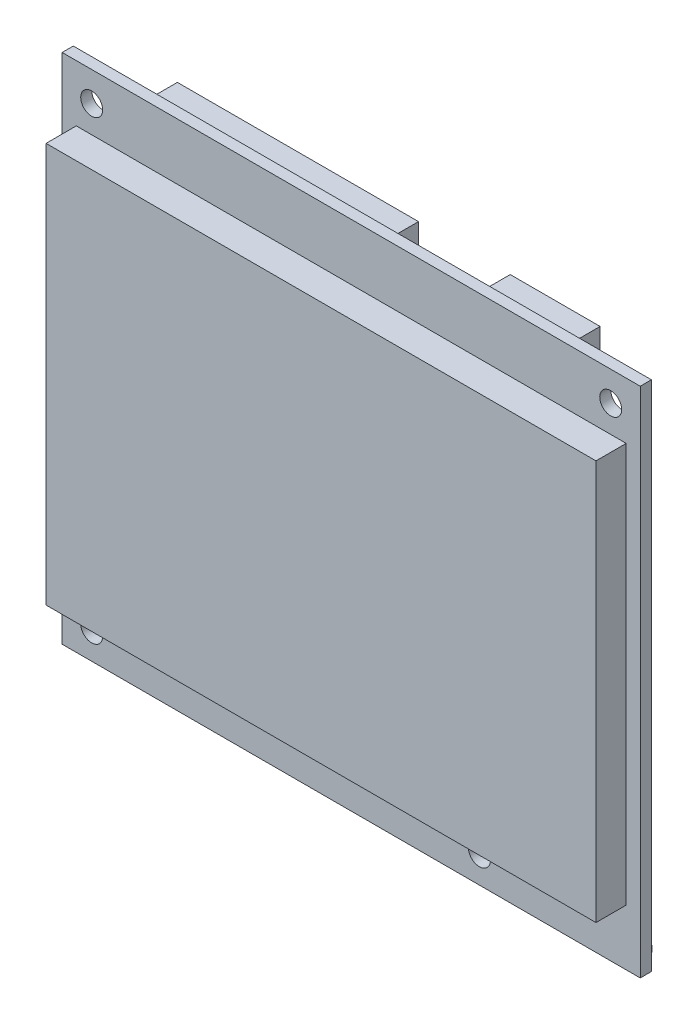
SolidWorks part; units mm, degrees
ref_plane "Front Plane" through (0, 0, 0) normal (0, 0, 1) x (1, 0, 0)
ref_plane "Top Plane" through (0, 0, 0) normal (0, 1, 0) x (1, 0, 0)
ref_plane "Right Plane" through (0, 0, 0) normal (1, 0, 0) x (0, 0, -1)
sketch "Sketch1" plane through (0, 0, 0) normal (0, 0, -1) x (-1, 0, 0)
  line L1 (-32.25, -24.25) -> (32.25, -24.25) construction
  line L2 (-32.25, -24.25) -> (-32.25, 24.25) construction
  line L3 (-32.25, 24.25) -> (32.25, 24.25) construction
  line L4 (32.25, -24.25) -> (32.25, 24.25) construction
  line L5 (-32.25, -24.25) -> (32.25, 24.25) construction
  line L6 (-32.25, 24.25) -> (32.25, -24.25) construction
  line L7 (-36, 28) -> (41.7, 28) construction
  line L8 (-36, 28) -> (-36, -28.5) construction
  line L9 (-36, -28.5) -> (41.7, -28.5) construction
  line L10 (41.7, 28) -> (41.7, -28.5) construction
  line L11 (-37.9864, 35.9904) -> (43.7, 35.9904)
  line L12 (-37.9864, 35.9904) -> (-37.9864, -36.425)
  line L13 (-37.9864, -36.425) -> (43.7, -36.425)
  line L14 (43.7, 35.9904) -> (43.7, -36.425)
  point P0 (0, 0)
  dimension "D1" = 64.5
  dimension "D2" = 48.5
  dimension "D3" = 3.75
  dimension "D4" = 3.75
  dimension "D5" = 56.5
  dimension "D6" = 77.7
  dimension "D7" = 7.925
  dimension "D8" = 72.4154
  dimension "D9" = 81.6864
  dimension "D10" = 2
extrude "Boss-Extrude1" add sketch "Sketch1" along normal blind 1.5748
sketch "Sketch2" plane through (0, 0, 0) normal (0, 0, -1) x (-1, 0, 0)
  line L1 (-36, -28.5) -> (41.7, -28.5)
  line L2 (-36, -28.5) -> (-36, 28)
  line L3 (-36, 28) -> (41.7, 28)
  line L4 (41.7, -28.5) -> (41.7, 28)
  line L5 (41.7, 28) -> (49.6841, 28) construction
  line L6 (-36, 28) -> (-43.9841, 28) construction
  line L10 (-32.25, -24.25) -> (32.25, -24.25) construction
  line L11 (-32.25, -24.25) -> (-32.25, 24.25) construction
  line L12 (-32.25, 24.25) -> (32.25, 24.25) construction
  line L13 (32.25, -24.25) -> (32.25, 24.25) construction
  line L14 (-32.25, -24.25) -> (32.25, 24.25) construction
  line L15 (-32.25, 24.25) -> (32.25, -24.25) construction
  point P0 (0, 0)
  point P14 (0, 0)
  dimension "D1" = 56.5
  dimension "D2" = 77.7
  dimension "D3" = 3.75
  dimension "D4" = 48.5
  dimension "D5" = 64.5
  dimension "D6" = 3.75
extrude "Boss-Extrude2" add sketch "Sketch2" against normal blind 4.27
sketch "Sketch3" plane through (0, 0, -1.5748) normal (0, 0, 1) x (1, 0, 0)
  line L1 (25.66, 33.8141) -> (12.96, 33.8141)
  line L2 (25.66, 33.8141) -> (25.66, 28.7341)
  line L3 (25.66, 28.7341) -> (12.96, 28.7341)
  line L4 (12.96, 33.8141) -> (12.96, 28.7341)
  line L6 (0, 33.8141) -> (-34.0711, 33.8141)
  line L7 (0, 33.8141) -> (0, 28.7341)
  line L8 (0, 28.7341) -> (-34.0711, 28.7341)
  line L9 (-34.0711, 33.8141) -> (-34.0711, 28.7341)
  line L10 (-34.0711, -29.1593) -> (0, -29.1593)
  line L11 (-34.0711, -29.1593) -> (-34.0711, -34.2393)
  line L12 (-34.0711, -34.2393) -> (0, -34.2393)
  line L13 (0, -29.1593) -> (0, -34.2393)
  dimension "D1" = 5.08
  dimension "D2" = 12.7
sketch "Sketch4" plane through (0, 0, -1.5748) normal (0, 0, -1) x (-1, 0, 0)
  line L0 (43.7, 35.9904) -> (-37.9864, 35.9904) construction
  line L1 (-37.9864, 35.9904) -> (-37.9864, -36.425) construction
  line L2 (43.7, -36.425) -> (43.7, 35.9904) construction
  line L3 (-37.9864, -36.425) -> (43.7, -36.425) construction
  line L4 (-37.9864, 35.9904) -> (-37.9864, -36.425) construction
  circle A0 centre (39.525, 31.8154) radius 1.55
  circle A1 centre (39.525, -32.625) radius 1.55
  circle A2 centre (-15.2614, -32.625) radius 1.55
  circle A3 centre (-33.8114, 31.8154) radius 1.55
  dimension "D3" = 3.1
  dimension "D1" = 4.175
  dimension "D2" = 4.175
  dimension "D4" = 4.175
  dimension "D5" = 3.8
  dimension "D6" = 22.725
extrude "Cut-Extrude1" cut sketch "Sketch4" against normal through all
extrude "Boss-Extrude3" add sketch "Sketch3" against normal blind 5.08
sketch "Sketch5" plane through (0, 0, -1.5748) normal (0, 0, -1) x (-1, 0, 0)
  line L0 (19.4766, 13.5356) -> (30.7313, 2.2809)
  line L1 (30.7313, 2.2809) -> (19.4766, -8.9738)
  line L2 (19.4766, -8.9738) -> (8.2218, 2.2809)
  line L3 (8.2218, 2.2809) -> (19.4766, 13.5356)
  line L5 (-15.8477, -24.7973) -> (-26.991, -24.7973)
  line L6 (-15.8477, -24.7973) -> (-15.8477, -9.9767)
  line L7 (-15.8477, -9.9767) -> (-26.991, -9.9767)
  line L8 (-26.991, -24.7973) -> (-26.991, -9.9767)
  line L9 (-37.0611, -34.1253) -> (-31.3584, -34.1253)
  line L10 (-37.0611, -34.1253) -> (-37.0611, -35.0607)
  line L11 (-37.0611, -35.0607) -> (-31.3584, -35.0607)
  line L12 (-31.3584, -34.1253) -> (-31.3584, -35.0607)
extrude "Boss-Extrude4" add sketch "Sketch5" along normal blind 1
